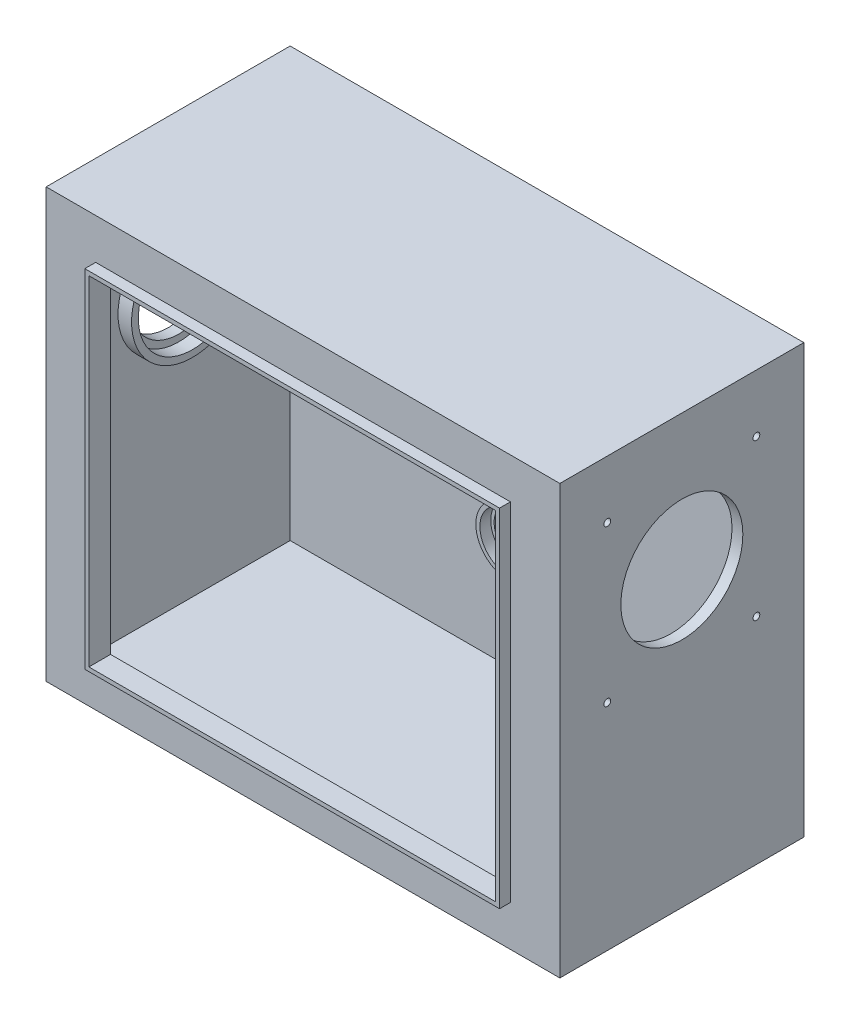
SolidWorks part; units mm, degrees
ref_plane "Alzado" through (0, 0, 0) normal (0, 0, 1) x (1, 0, 0)
ref_plane "Planta" through (0, 0, 0) normal (0, 1, 0) x (1, 0, 0)
ref_plane "Vista lateral" through (0, 0, 0) normal (1, 0, 0) x (0, 0, -1)
sketch "Croquis1" plane through (0, 0, 0) normal (0, 0, 1) x (1, 0, 0)
  line L0 (-189.5, 158) -> (189.5, 158)
  line L1 (-181.5, -150) -> (181.5, -150) construction
  line L2 (-181.5, -150) -> (-181.5, 150) construction
  line L3 (-181.5, 150) -> (181.5, 150) construction
  line L4 (181.5, -150) -> (181.5, 150) construction
  line L5 (-181.5, -150) -> (181.5, 150) construction
  line L6 (-181.5, 150) -> (181.5, -150) construction
  line L7 (189.5, -158) -> (189.5, 158)
  line L8 (-189.5, -158) -> (189.5, -158)
  line L9 (-189.5, -158) -> (-189.5, 158)
  point P0 (0, 0)
  dimension "D1" = 363
  dimension "D2" = 300
  dimension "D3" = 8
extrude "Saliente-Extruir1" add sketch "Croquis1" along normal blind 180
shell "Vaciado1" thickness 8 removed face at (0, 0, 180)
sketch "Croquis2" plane through (-189.5, 0, 0) normal (-1, 0, 0) x (0, 0, 1)
  line L0 (0, 158) -> (90, 158) construction
  line L1 (180, 158) -> (0, 158) construction
  circle A0 centre (90, 58) radius 35
extrude "Cortar-Extruir4" cut sketch "Croquis2" against normal blind 20 contours A0
sketch "Croquis4" plane through (-181.5, 0, 0) normal (1, 0, 0) x (0, 0, -1)
  circle A1 centre (-90, 58) radius 40
  circle A2 centre (-90, 58) radius 45
extrude "Saliente-Extruir4" add sketch "Croquis4" along normal blind 10
sketch "Croquis6" plane through (189.5, 0, 0) normal (1, 0, 0) x (0, 0, -1)
  line L0 (-90, 158) -> (-90, 58) construction
  line L1 (-180, 158) -> (0, 158) construction
  circle A0 centre (-90, 58) radius 45
  dimension "D1" = 90
extrude "Cortar-Extruir6" cut sketch "Croquis6" against normal blind 10 contours A0
sketch "Croquis7" plane through (0, 0, 8) normal (0, 0, 1) x (1, 0, 0)
  circle A3 centre (-2.5, -53) radius 21
  circle A4 centre (-2.5, -53) radius 24
  dimension "D1" = 42
  dimension "D2" = 48
extrude "Saliente-Extruir9" add sketch "Croquis7" along normal blind 18
ref_plane "Plano6" through (0, 0, 180) normal (0, 0, 1) x (1, 0, 0)
sketch "Croquis11" plane through (0, 0, 180) normal (0, 0, 1) x (1, 0, 0)
  line L1 (181.5, 150) -> (-181.5, 150)
  line L2 (181.5, 150) -> (181.5, -150)
  line L3 (181.5, -150) -> (-181.5, -150)
  line L4 (-181.5, 150) -> (-181.5, -150)
  line L5 (181.5, 150) -> (-181.5, -150) construction
  line L6 (181.5, -150) -> (-181.5, 150) construction
  line L7 (-150, 125) -> (150, 125)
  line L8 (-150, 125) -> (-150, -125)
  line L9 (-150, -125) -> (150, -125)
  line L10 (150, 125) -> (150, -125)
  line L11 (-150, 125) -> (150, -125) construction
  line L12 (-150, -125) -> (150, 125) construction
  point P0 (0, 0)
  point P7 (0, 0)
  dimension "D1" = 300
  dimension "D2" = 250
extrude "Saliente-Extruir10" add sketch "Croquis11" against normal blind 8
sketch "Croquis12" plane through (0, 0, 180) normal (0, 0, 1) x (1, 0, 0)
  line L1 (150, -125) -> (-150, -125)
  line L2 (150, -125) -> (150, 125)
  line L3 (150, 125) -> (-150, 125)
  line L4 (-150, -125) -> (-150, 125)
  line L5 (150, -125) -> (-150, 125) construction
  line L6 (150, 125) -> (-150, -125) construction
  line L7 (153, -128) -> (-153, -128)
  line L8 (153, -128) -> (153, 128)
  line L9 (153, 128) -> (-153, 128)
  line L10 (-153, -128) -> (-153, 128)
  line L11 (153, -128) -> (-153, 128) construction
  line L12 (153, 128) -> (-153, -128) construction
  point P0 (0, 0)
  point P8 (0, 0)
  dimension "D1" = 3
  dimension "D2" = 3
extrude "Saliente-Extruir11" add sketch "Croquis12" along normal blind 8
sketch "Croquis13" plane through (0, 0, 180) normal (0, 0, 1) x (1, 0, 0)
  line L0 (189.5, 158) -> (-189.5, 158) construction
  line L1 (-179, 68) -> (-163, 68)
  line L2 (-179, 68) -> (-179, 48)
  line L3 (-179, 48) -> (-163, 48)
  line L4 (-163, 68) -> (-163, 48)
  line L5 (-179, 68) -> (-163, 48) construction
  line L6 (-179, 48) -> (-163, 68) construction
  line L7 (-153, 128) -> (-153, -128) construction
  point P0 (-171, 58)
  dimension "D1" = 100
  dimension "D2" = 20
  dimension "D3" = 16
  dimension "D4" = 10
sketch "Croquis17" plane through (0, 0, 180) normal (0, 0, 1) x (1, 0, 0)
  line L1 (-153, 128) -> (-153, -128) construction
  line L2 (-179, -48) -> (-163, -48)
  line L3 (-179, -48) -> (-179, -68)
  line L4 (-179, -68) -> (-163, -68)
  line L5 (-163, -48) -> (-163, -68)
  line L6 (-179, -48) -> (-163, -68) construction
  line L7 (-179, -68) -> (-163, -48) construction
  line L8 (-189.5, -158) -> (189.5, -158) construction
  point P2 (-171, -58)
  dimension "D1" = 20
  dimension "D2" = 16
  dimension "D3" = 10
  dimension "D4" = 100
sketch "Croquis20" plane through (0, 0, 8) normal (0, 0, 1) x (1, 0, 0)
  circle A0 centre (-2.5, -53) radius 18.5
  circle A1 centre (-2.5, -53) radius 21
  circle A2 centre (-2.5, -53) radius 21 construction
  dimension "D1" = 37
extrude "Saliente-Extruir19" add sketch "Croquis20" along normal blind 10
hole_wizard "Taladro roscado M63" positions "Croquis3D6" profile "Croquis26" tap size "M6" standard "DIN" end condition through all
sketch3d "Croquis3D6"
  line L2 (-189.5, 0.5, 145) -> (-189.5, 115.5, 145) construction
  line L3 (-189.5, 0.5, 145) -> (-189.5, 0.5, 35) construction
  line L4 (-189.5, 0.5, 35) -> (-189.5, 115.5, 35) construction
  line L5 (-189.5, 115.5, 145) -> (-189.5, 115.5, 35) construction
  line L6 (-189.5, 0.5, 145) -> (-189.5, 115.5, 35) construction
  line L7 (-189.5, 0.5, 35) -> (-189.5, 115.5, 145) construction
  circle A1 centre (-189.5, 58, 90) radius 35 construction
  point P0 (-189.5, 115.5, 35)
  point P2 (-189.5, 115.5, 145)
  point P4 (-189.5, 0.5, 145)
  point P6 (-189.5, 0.5, 35)
  point P265 (-189.5, 58, 90)
  point P268 (-224.5, 58, 90)
  dimension "D1" = 115
  dimension "D2" = 0
  dimension "D3" = 110
sketch "Croquis26" plane through (-189.5, 115.5, 35) normal (0, 1, 0) x (0, 0, 1)
  line L0 (0, 0) -> (0, 379)
  line L1 (0, 379) -> (2.5, 379)
  line L2 (2.5, 379) -> (2.5, 0)
  line L5 (2.5, 0) -> (0, 0)
  line L11 (0, -6.35) -> (0, 107.95) construction
  dimension "Diámetro de perforador para roscar hasta el siguiente" = 5
  dimension "Profundidad de perforador para roscar hasta el siguiente" = 379
cosmetic thread "Rosca de taladro1" parameters "D2"=6
cosmetic thread "Rosca de taladro2" parameters "D2"=6
cosmetic thread "Rosca de taladro3" parameters "D2"=6
cosmetic thread "Rosca de taladro4" parameters "D2"=6
sketch "Croquis27" plane through (0, 0, 0) normal (0, 0, -1) x (-1, 0, 0)
  circle A0 centre (2.5, -53) radius 11
  circle A1 centre (2.5, -53) radius 21 construction
  dimension "D1" = 22
extrude "Cortar-Extruir7" cut sketch "Croquis27" against normal up to surface (8 mm away) up to face at (-26.5, -53, 8)
